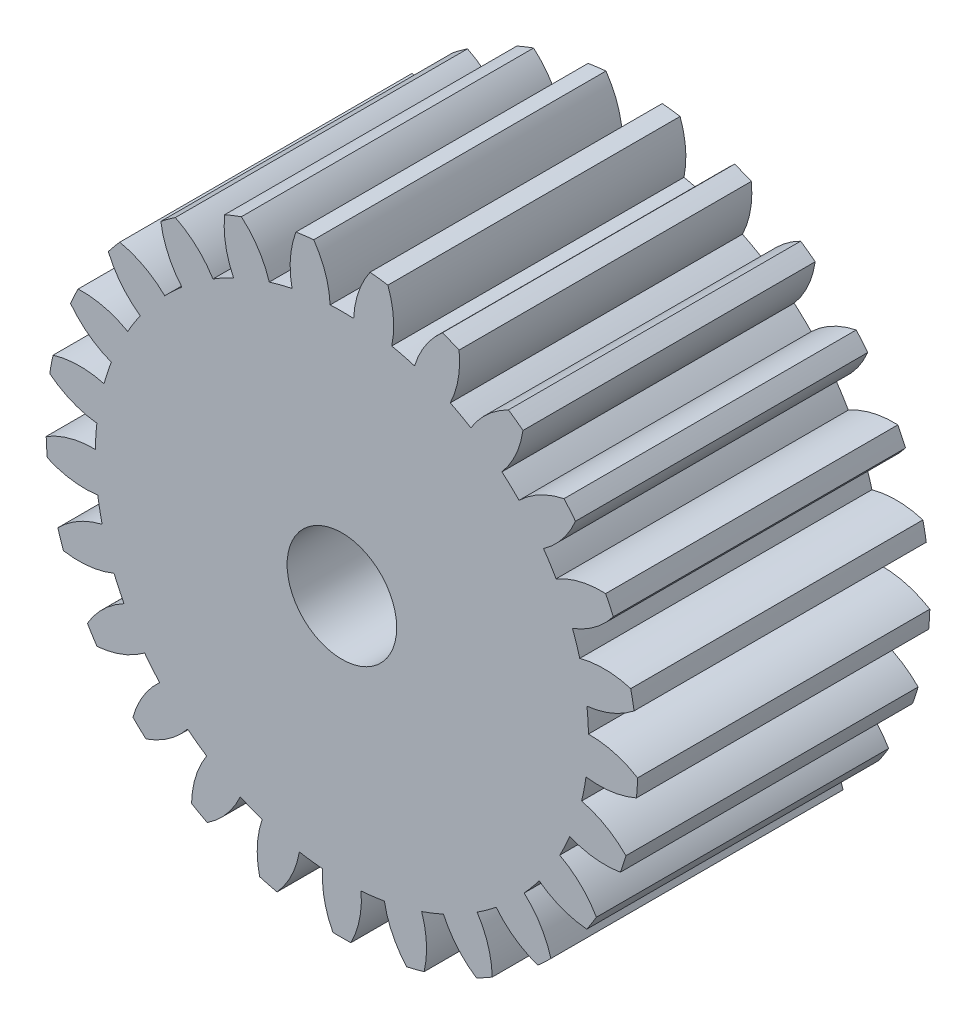
SolidWorks part; units mm, degrees
material "Нержавеющая сталь (ферритная)"
ref_plane "Спереди" through (0, 0, 0) normal (0, 0, 1) x (1, 0, 0)
ref_plane "Сверху" through (0, 0, 0) normal (0, 1, 0) x (1, 0, 0)
ref_plane "Справа" through (0, 0, 0) normal (1, 0, 0) x (0, 0, -1)
sketch "Эскиз1" plane through (0, 0, 0) normal (0, 0, 1) x (1, 0, 0)
  circle A0 centre (0, 0) radius 8.1
  circle A1 centre (0, 0) radius 1.5
  dimension "D1" = 16.2
  dimension "D2" = 3
extrude "Бобышка-Вытянуть1" add sketch "Эскиз1" along normal mid plane 8
sketch "Эскиз2" plane through (0, 0, 0) normal (0, 0, 1) x (1, 0, 0)
  line L0 (0, 0) -> (0, 8.1) construction
  line L1 (-0.3216, 6.7423) -> (0, 0) construction
  line L2 (-0.4709, 7.4852) -> (0, 6.1913) construction
  line L3 (-0.4709, 7.4852) -> (0.4709, 7.4852) construction
  line L4 (0.4709, 7.4852) -> (1.4054, 7.3672) construction
  line L5 (0, 0) -> (0.9381, 7.4262) construction
  arc A0 (1.4054, 7.3672) -> (-0.4709, 7.4852) centre (0, 0) ccw construction
  arc A1 (0.3216, 6.7423) -> (-0.3216, 6.7423) centre (0, 0) ccw
  circle A2 centre (0, 0) radius 8.1 construction
  arc A3 (0.7707, 8.0632) -> (-0.7707, 8.0632) centre (0, 0) ccw
  arc A4 (0.3216, 6.7423) -> (0.7707, 8.0632) centre (2.8423, 6.6221) cw
  arc A5 (-0.3216, 6.7423) -> (-0.7707, 8.0632) centre (-2.8423, 6.6221) ccw
  point P0 (1.4034, 6.6025)
  dimension "D1" = 13.5
  dimension "D2" = 15
  dimension "D3" = 20
  dimension "D4" = 7.2
extrude "Вырез-Вытянуть1" cut sketch "Эскиз2" against normal through all both and the other way through all
pattern_circular "Круговой массив1" count 25 over 360 about axis through (0, 0, 4) along (0, 0, -1) of "Вырез-Вытянуть1"
